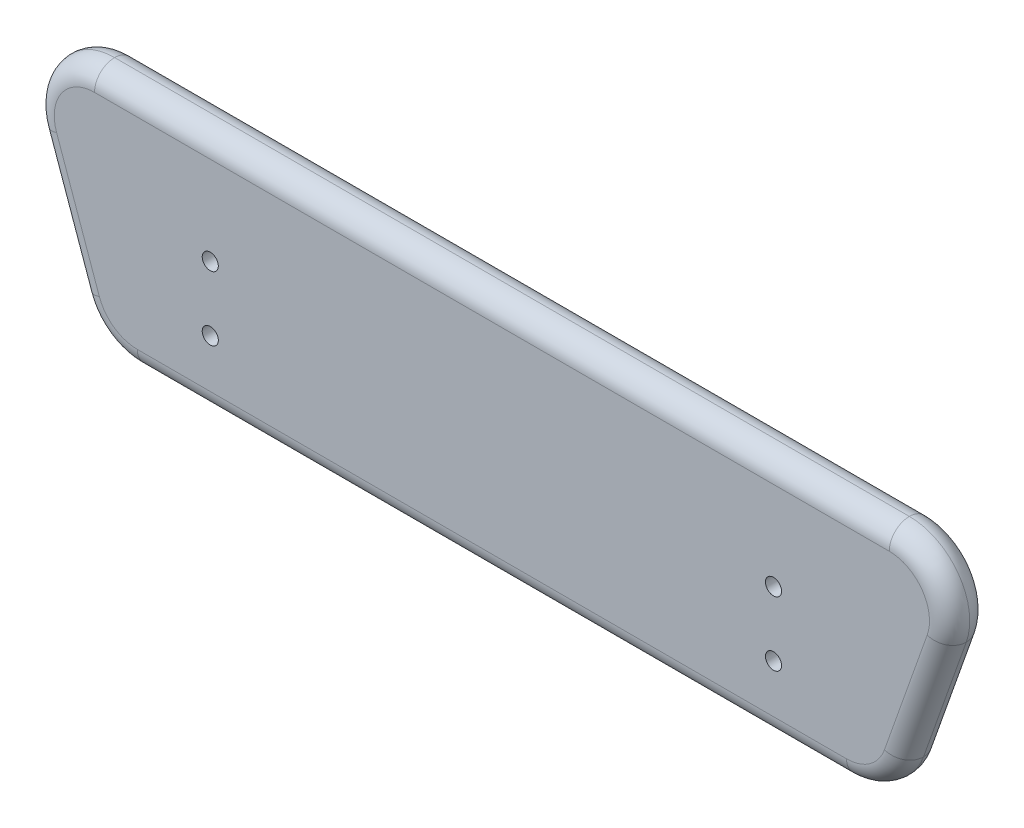
SolidWorks part; units mm, degrees
ref_plane "前基準面" through (0, 0, 0) normal (0, 0, 1) x (1, 0, 0)
ref_plane "上基準面" through (0, 0, 0) normal (0, 1, 0) x (1, 0, 0)
ref_plane "右基準面" through (0, 0, 0) normal (1, 0, 0) x (0, 0, -1)
sketch "草圖1" plane through (0, 0, 0) normal (0, 0, 1) x (1, 0, 0)
  line L0 (-123.9462, 3.4978) -> (-102.6991, -56.5022)
  line L1 (-123.9462, 3.4978) -> (116.0538, 3.4978)
  line L3 (-102.6991, -56.5022) -> (94.8067, -56.5022)
  line L5 (116.0538, 3.4978) -> (94.8067, -56.5022)
  dimension "D1" = 240
  dimension "D3" = 70.5
  dimension "D4" = 70.5
extrude "填料-伸長1" add sketch "草圖1" along normal blind 10
fillet "圓角1" radius 15 4 edges at (116.0538, 3.4978, 5) (94.8067, -56.5022, 5) (-102.6991, -56.5022, 5) (-123.9462, 3.4978, 5)
fillet "圓角2" radius 5 16 edges at (107.0789, -2.8451, 10) (103.6571, -31.5093, 10) (92.8629, -53.7519, 10) (-3.9462, -56.5022, 10) (-100.7553, -53.7519, 10) (-111.5495, -31.5093, 10) (-114.9713, -2.8451, 10) (-3.9462, 3.4978, 10) (-114.9713, -2.8451, 0) (-111.5495, -31.5093, 0) (-100.7553, -53.7519, 0) (-3.9462, -56.5022, 0) (92.8629, -53.7519, 0) (103.6571, -31.5093, 0) (107.0789, -2.8451, 0) (-3.9462, 3.4978, 0)
sketch "草圖2" plane through (0, 0, 10) normal (0, 0, 1) x (1, 0, 0)
  circle A0 centre (-73.9462, -23.5022) radius 2
  circle A1 centre (-73.9462, -39.5022) radius 2
  circle A2 centre (66.0538, -39.5022) radius 2
  circle A3 centre (66.0538, -23.5022) radius 2
  dimension "D3" = 16
extrude "除料-伸長1" cut sketch "草圖2" against normal blind 7.5
